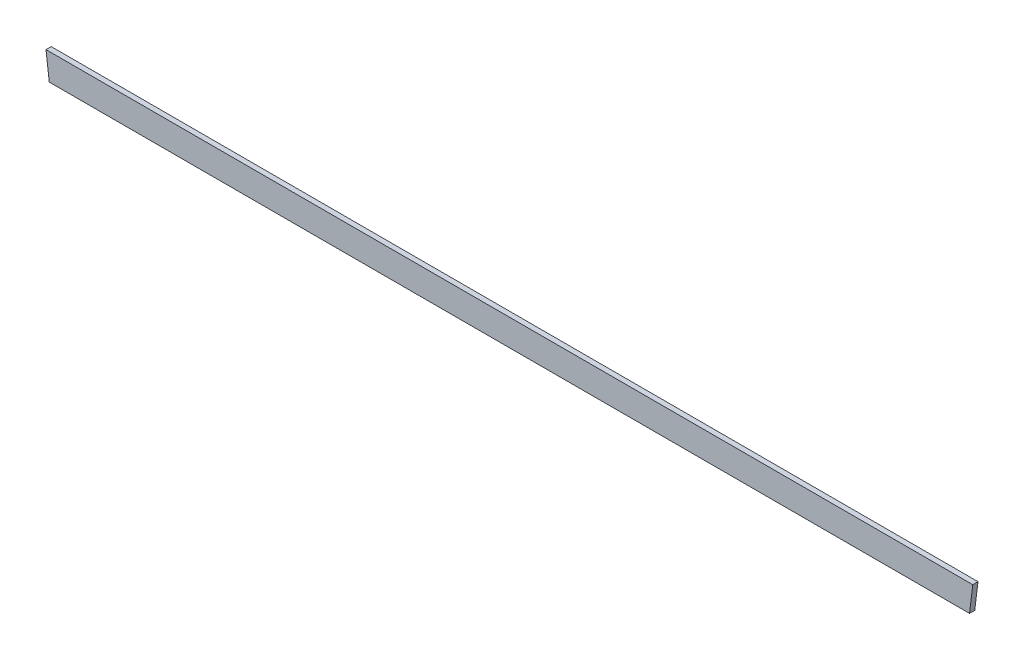
SolidWorks part; units mm, degrees
ref_plane "Front Plane" through (0, 0, 0) normal (0, 0, 1) x (1, 0, 0)
ref_plane "Top Plane" through (0, 0, 0) normal (0, 1, 0) x (1, 0, 0)
ref_plane "Right Plane" through (0, 0, 0) normal (1, 0, 0) x (0, 0, -1)
ref_axis "Axis1" through (0, -55, 0) along (0, 1, 0)
sketch "Sketch1" plane through (0, 0, 0) normal (0, 0, 1) x (1, 0, 0)
  line L1 (-881.4925, -114.3) -> (881.4925, -114.3)
  line L3 (887.73, -63.5) -> (881.4925, -114.3)
  line L5 (-881.4925, -114.3) -> (-887.73, -63.5)
  line L6 (887.73, -63.5) -> (-887.73, -63.5)
  point P7 (0, -63.5)
  dimension "D1" = 50.8
  dimension "D2" = 1775.46
  dimension "D3" = 63.5
  dimension "D4" = 97
  dimension "D7" = 97
extrude "Boss-Extrude1" add sketch "Sketch1" along normal blind 10
